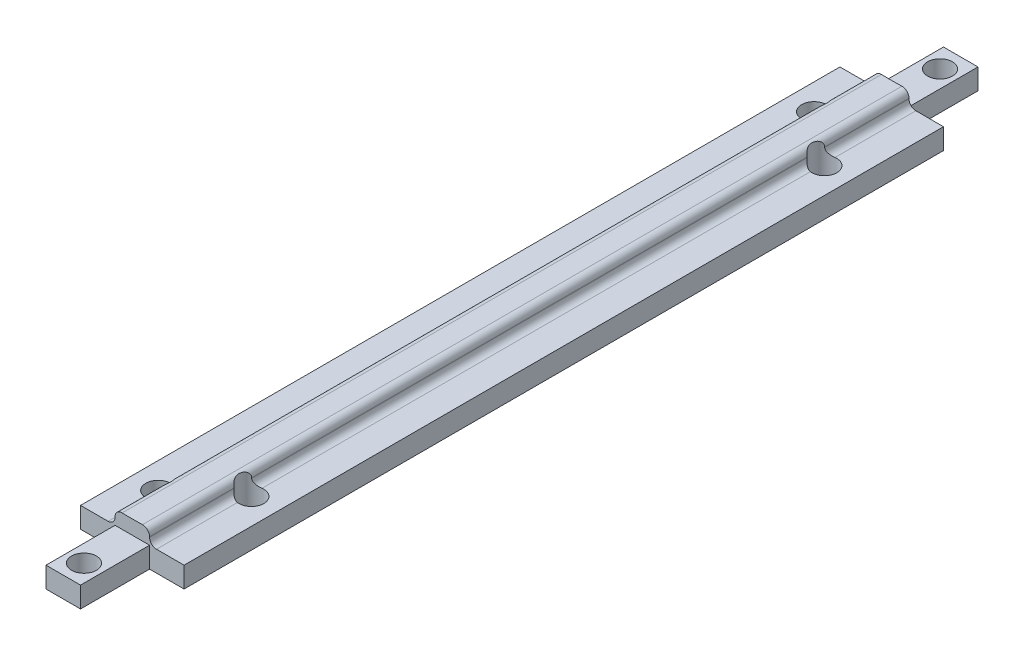
SolidWorks part; units mm, degrees
ref_plane "Front Plane" through (0, 0, 0) normal (0, 0, 1) x (1, 0, 0)
ref_plane "Top Plane" through (0, 0, 0) normal (0, 1, 0) x (1, 0, 0)
ref_plane "Right Plane" through (0, 0, 0) normal (1, 0, 0) x (0, 0, -1)
sketch "Sketch1" plane through (0, 0, 0) normal (0, 1, 0) x (1, 0, 0)
  line L1 (-2.5, -55) -> (2.5, -55)
  line L2 (-2.5, -55) -> (-2.5, 55)
  line L3 (-2.5, 55) -> (2.5, 55)
  line L4 (2.5, -55) -> (2.5, 55)
  line L5 (-2.5, -55) -> (2.5, 55) construction
  line L6 (-2.5, 55) -> (2.5, -55) construction
  point P0 (0, 0)
  dimension "D1" = 5
  dimension "D2" = 110
extrude "Boss-Extrude1" add sketch "Sketch1" along normal blind 3
ref_plane "Plane3" through (0, 0, 0) normal (0, 0, 1) x (1, 0, 0)
sketch "Sketch3" plane through (0, 0, 0) normal (0, 0, 1) x (1, 0, 0)
  line L0 (-2.5, 3) -> (-2.5, 5.103)
  line L1 (-2.5, 5.103) -> (2.5, 5.103) construction
  line L2 (2.5, 5.103) -> (2.5, 3)
  line L3 (0, 5.103) -> (0, 64.05) construction
  line L4 (-2.5, 0) -> (2.5, 0)
  line L5 (2.5, 0) -> (2.5, 3)
  line L6 (2.5, 3) -> (-2.5, 3)
  line L7 (-2.5, 3) -> (-2.5, 0)
  line L8 (-2.5, 0) -> (2.5, 0)
  line L9 (2.5, 0) -> (2.5, 3)
  line L11 (-2.5, 3) -> (-2.5, 0)
  arc A0 (-2.5, 5.103) -> (2.5, 5.103) centre (0, 64.05) ccw
  dimension "D1" = 0
extrude "Boss-Extrude2" add sketch "Sketch3" along normal up to surface (55 mm away) up to face at (0, 1.5, 55)
sketch "Sketch7" plane through (0, 0, 0) normal (0, 0, -1) x (-1, 0, 0)
  line L3 (-2.5, 5.103) -> (-2.5, 3)
  line L4 (-2.5, 3) -> (2.5, 3)
  line L5 (2.5, 3) -> (2.5, 5.103)
  line L6 (-2.5, 5.103) -> (-2.5, 3)
  line L7 (-2.5, 3) -> (2.5, 3)
  line L8 (2.5, 3) -> (2.5, 5.103)
  arc A1 (-2.5, 5.103) -> (2.5, 5.103) centre (0, 64.05) ccw
  arc A2 (-2.5, 5.103) -> (2.5, 5.103) centre (0, 64.05) ccw
  dimension "D1" = 0
extrude "Boss-Extrude3" add sketch "Sketch7" along normal up to surface (55 mm away) up to face at (0, 1.5, -55)
sketch "Sketch8" plane through (0, 0, 0) normal (0, -1, 0) x (1, 0, 0)
  line L0 (2.5, 55) -> (2.5, -55) construction
  line L1 (-2.5, 55) -> (2.5, 55)
  line L2 (-2.5, 55) -> (-2.5, 65)
  line L3 (-2.5, 65) -> (2.5, 65)
  line L4 (2.5, 55) -> (2.5, 65)
  line L5 (0, 0) -> (17.0745, 0) construction
  line L6 (-2.5, -65) -> (2.5, -65)
  line L7 (2.5, -55) -> (2.5, -65)
  line L8 (-2.5, -55) -> (2.5, -55)
  line L9 (-2.5, -55) -> (-2.5, -65)
  dimension "D1" = 10
extrude "Boss-Extrude4" add sketch "Sketch8" against normal blind 3
sketch "Sketch6" plane through (0, 3, 0) normal (0, 1, 0) x (1, 0, 0)
  line L0 (0, -65) -> (0, -62) construction
  line L2 (0, 0) -> (12.4428, 0) construction
  line L3 (-5.6053, 0) -> (5.6053, 0) construction
  line L4 (2.5, -65) -> (-2.5, -65) construction
  circle A0 centre (0, -62) radius 1.8
  circle A1 centre (0, 62) radius 1.8
  dimension "D1" = 3.6
  dimension "D2" = 3
extrude "Cut-Extrude1" cut sketch "Sketch6" against normal through all
sketch "Sketch9" plane through (0, 0, 0) normal (0, -1, 0) x (1, 0, 0)
  line L0 (2.5, -55) -> (-2.5, -55) construction
  line L1 (-2.5, 55) -> (2.5, 55) construction
  line L2 (2.5, -55) -> (-2.5, -55) construction
  line L3 (-2.5, 55) -> (2.5, 55) construction
  line L4 (-2.5, -65) -> (-2.5, 65) construction
  line L5 (-7.5, -55) -> (7.5, -55)
  line L6 (-7.5, -55) -> (-7.5, 55)
  line L7 (-7.5, 55) -> (7.5, 55)
  line L8 (7.5, -55) -> (7.5, 55)
  line L9 (-2.5, -65) -> (-2.5, 65) construction
  point P8 (0, -55)
  point P9 (0, -55)
  point P10 (0, 55)
  point P11 (0, 55)
  dimension "D1" = 5
extrude "Boss-Extrude5" add sketch "Sketch9" against normal up to surface (3 mm away) up to face at (0, 3, 63.8)
fillet "Fillet1" radius 1 4 edges at (-2.5, 5.103, 0) (2.5, 5.103, 0) (2.5, 3, 0) (-2.5, 3, 0)
sketch "Sketch10" plane through (0, 3, 0) normal (0, 1, 0) x (1, 0, 0)
  line L0 (0, -55) -> (0, -47.5) construction
  line L1 (-1.475, -55) -> (1.475, -55) construction
  line L2 (0, -47.5) -> (-3.75, -47.5) construction
  line L3 (-3.75, -47.5) -> (-7.5, -47.5) construction
  line L4 (-7.5, -55) -> (-7.5, 55) construction
  line L5 (0, -47.5) -> (0, -41.5) construction
  line L6 (0, -41.5) -> (3.75, -41.5) construction
  line L7 (3.75, -41.5) -> (7.5, -41.5) construction
  line L8 (7.5, 55) -> (7.5, -55) construction
  line L9 (-3.5, -55) -> (-7.5, -55) construction
  line L10 (-7.5, 0) -> (7.5, 0) construction
  circle A0 centre (-3.75, -47.5) radius 1.8
  circle A1 centre (3.75, -41.5) radius 1.8
  circle A2 centre (3.75, 41.5) radius 1.8
  circle A3 centre (-3.75, 47.5) radius 1.8
  dimension "D1" = 3.6
  dimension "D2" = 6
  dimension "D3" = 7.5
extrude "Cut-Extrude2" cut sketch "Sketch10" against normal through all both and the other way through all
